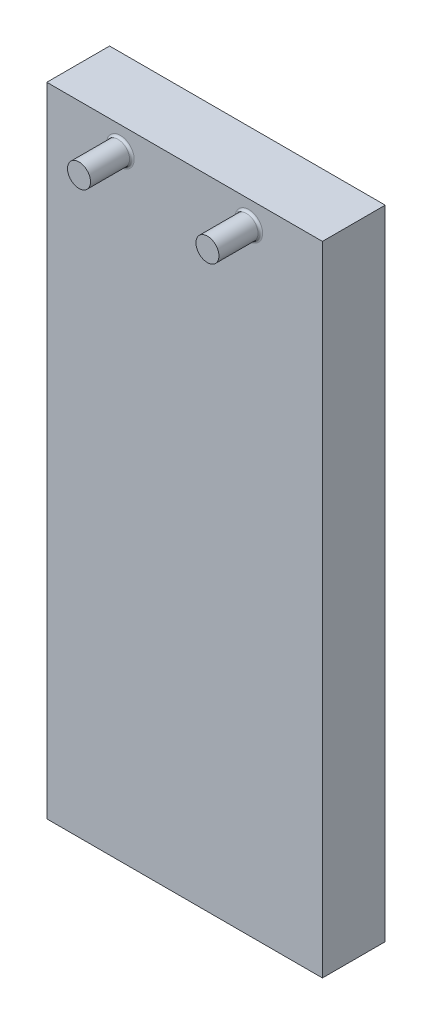
SolidWorks part; units mm, degrees
ref_plane "Front Plane" through (0, 0, 0) normal (0, 0, 1) x (1, 0, 0)
ref_plane "Top Plane" through (0, 0, 0) normal (0, 1, 0) x (1, 0, 0)
ref_plane "Right Plane" through (0, 0, 0) normal (1, 0, 0) x (0, 0, -1)
sketch "Sketch1" plane through (0, 0, 0) normal (0, 1, 0) x (1, 0, 0)
  line L1 (-59.92, -13.65) -> (59.92, -13.65)
  line L2 (-59.92, -13.65) -> (-59.92, 13.65)
  line L3 (-59.92, 13.65) -> (59.92, 13.65)
  line L4 (59.92, -13.65) -> (59.92, 13.65)
  line L5 (-59.92, -13.65) -> (59.92, 13.65) construction
  line L6 (-59.92, 13.65) -> (59.92, -13.65) construction
  point P0 (0, 0)
  dimension "D1" = 119.84
  dimension "D2" = 27.3
extrude "Boss-Extrude1" add sketch "Sketch1" along normal blind 277.37
sketch "Sketch2" plane through (0, 0, 13.65) normal (0, 0, 1) x (1, 0, 0)
  line L0 (-59.92, 257.37) -> (59.92, 257.37)
  line L1 (-59.92, 277.37) -> (-59.92, 0) construction
  line L2 (59.92, 277.37) -> (59.92, 0) construction
  line L3 (-59.92, 277.37) -> (59.92, 277.37) construction
  line L4 (-59.92, 257.37) -> (-59.92, 277.37)
  line L5 (-59.92, 267.37) -> (59.92, 267.37) construction
  circle A2 centre (-27.92, 267.37) radius 5
  circle A3 centre (27.92, 267.37) radius 5
  dimension "D4" = 10
  dimension "D1" = 20
  dimension "D2" = 32
  dimension "D3" = 32
extrude "Boss-Extrude2" add sketch "Sketch2" along normal blind 18 contours L5 A3 | A3 L5 | L5 A2 | A2 L5 region at (-27.92, 269.4921, 13.65) region at (27.92, 269.4921, 13.65) region at (27.92, 265.2479, 13.65) region at (-27.92, 265.2479, 13.65)
fillet "Fillet1" radius 1 2 edges at (22.92, 267.37, 13.65) (-32.92, 267.37, 13.65)
equation "\"PCWidth\"= 340mm'Distance of longest part parallel to GPU(ussually GPU)"
equation "\"PCLength\"= 150mm'Length across I/O from PS to GPU"
equation "\"PCHeight\"= 190mm'Tallest point with mobo laying flat"
equation "\"WallThickness\"= 9mm'Thickness of each outer tank wall"
equation "\"ThermoBarrierThickness\"= 6mm'Thickness of barrier between hot side and cold side"
equation "\"HotSideGap\"= 15mm'Space in the hot side that hot fluid flows into"
equation "\"PCClearance\"= 40mm'Clearance from top of tank to top of PC"
equation "\"RadiatorHeight\"= 277.37mm'Final Height from ground of radiators"
equation "\"D1@Boss-Extrude1\"=\"RadiatorHeight\""
